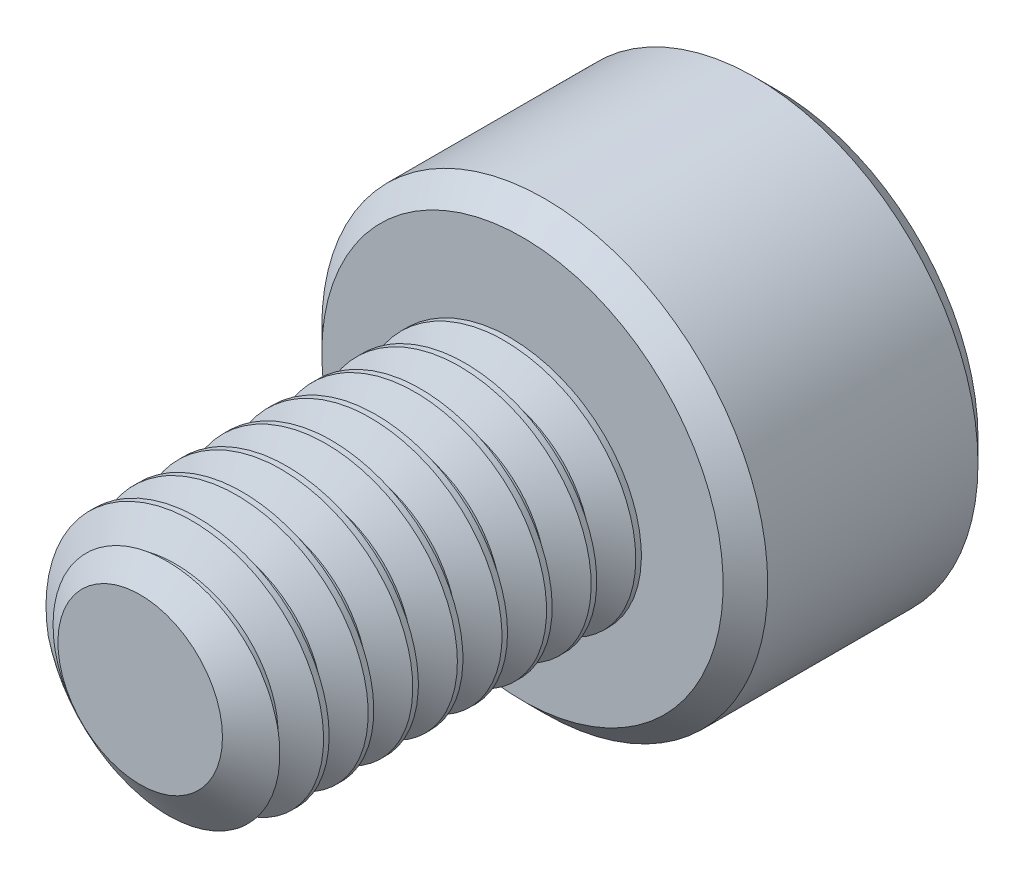
SolidWorks part; units mm, degrees
other "DetailItem1"
material "Stainless Steel (ferritic)"
ref_plane "Front Plane" through (0, 0, 0) normal (0, 0, 1) x (1, 0, 0)
ref_plane "Top Plane" through (0, 0, 0) normal (0, 1, 0) x (1, 0, 0)
ref_plane "Right Plane" through (0, 0, 0) normal (1, 0, 0) x (0, 0, -1)
sketch "Sketch1" plane through (0, 0, 0) normal (0, 0, 1) x (1, 0, 0)
  circle A0 centre (0, 0) radius 2
  dimension "OD" = 4
extrude "Extrude1" add sketch "Sketch1" against normal blind 6
sketch "Sketch2" plane through (0, 0, 0) normal (0, 0, 1) x (1, 0, 0)
  circle A0 centre (0, 0) radius 2 construction
  circle A1 centre (0, 0) radius 2
curve "Helix/Spiral1" pitch 0.7 height 6.7 radius 2 centre (0, 0, 0) axis (0, 0, -1) start towards (0, 1, 0) parameters "pitch"=0.7
sketch "Sketch3" plane through (0, 0, 0) normal (1, 0, 0) x (0, 0, -1)
  line L0 (-0.6125, 2) -> (-0.35, 1.5453)
  line L1 (-0.35, 1.5453) -> (-0.2625, 1.5453)
  line L2 (-0.2625, 1.5453) -> (0, 2)
  line L3 (-0.6125, 2) -> (0, 2)
  line L4 (-0.3062, 2) -> (-0.3062, 1.5453) construction
  line L5 (-0.4812, 1.7727) -> (-0.1312, 1.7727) construction
  line L6 (0, 2) -> (0, -2) construction
  dimension "D1" = 0.0875
  dimension "D2" = 0.35
  dimension "D3" = 60
sweep "Cut-Sweep1" cut profiles "Sketch3" path "Helix/Spiral1" align with end faces yes
sketch "Sketch4" plane through (0, 0, 0) normal (1, 0, 0) x (0, 0, -1)
  line L0 (0.4962, 2) -> (0, 1.2913)
  line L1 (0, 1.2913) -> (0, 2)
  line L2 (0.4962, 2) -> (0, 2)
  line L3 (-0.6125, 2) -> (0, 2) construction
  line L4 (0, 0) -> (7.0209, 0) construction
  dimension "D1" = 55
  dimension "D2" = 0.254
revolve "Cut-Revolve1" cut sketch "Sketch4" angle 360 about L4
sketch "Sketch6" plane through (0, 0, -6) normal (0, 0, -1) x (-1, 0, 0)
  circle A0 centre (0, 0) radius 3.5
  dimension "head dia" = 7
extrude "Extrude2" add sketch "Sketch6" along normal blind 4
sketch "Sketch7" plane through (0, 0, -10) normal (0, 0, -1) x (-1, 0, 0)
  line L1 (0, 1.7321) -> (-1.5, 0.866)
  line L2 (-1.5, 0.866) -> (-1.5, -0.866)
  line L3 (-1.5, -0.866) -> (0, -1.7321)
  line L4 (0, -1.7321) -> (1.5, -0.866)
  line L5 (1.5, -0.866) -> (1.5, 0.866)
  line L6 (1.5, 0.866) -> (0, 1.7321)
  circle A0 centre (0, 0) radius 1.5 construction
  dimension "hex dia" = 3
extrude "Cut-Extrude1" cut sketch "Sketch7" against normal blind 2.25
sketch "Sketch8" plane through (0, 0, -10) normal (0, 0, -1) x (-1, 0, 0)
  circle A0 centre (0, 0) radius 1.7321
extrude "Cut-Extrude2" cut sketch "Sketch8" against normal through all draft 45
chamfer "Chamfer1" distance 0.35 angle 45 2 edges at (-3.5, 0, -10) (-3.5, 0, -6)
sketch "Sketch10" plane through (0, 0, -6) normal (0, 0, 1) x (1, 0, 0)
  circle A1 centre (0, 0) radius 2
  circle A2 centre (0, 0) radius 2
  dimension "D1" = 0
ref_plane "Plane1" through (0, 0, 0) normal (0, 0, 1) x (1, 0, 0)
extrude "partial thread" [suppressed] add sketch "Sketch10" along normal up to surface (10 mm away) separate body up to plane "Plane1"
chamfer "Chamfer2" [suppressed] distance 0.08 angle 45
combine bodies "Combine1" [suppressed] operation type add bodies to combine 107 108
sketch "Sketch9" plane through (0, 0, 0) normal (1, 0, 0) x (0, 0, -1)
  line L0 (0, 2) -> (0, -2) construction
  line L1 (1.75, 2) -> (1.75, -2) construction
  dimension "D1" = 1.75
equation "\"D3@Helix/Spiral1\" = \"screw length@Extrude1\"+\"pitch@Helix/Spiral1\""
equation "\"D1@Sketch3\" = \"pitch@Helix/Spiral1\"*.125"
equation "\"D2@Sketch3\" = \"pitch@Helix/Spiral1\"*.5"
equation "\"D1@Cut-Extrude1\" = \"hex dia@Sketch7\"*.75"
equation "\"D1@Chamfer1\" = \"head dia@Sketch6\"*.05"
equation "\"D1@Sketch9\" = \"pitch@Helix/Spiral1\"*2.5"
equation "\"D1@Chamfer2\"=\"OD@Sketch1\"*.02"
